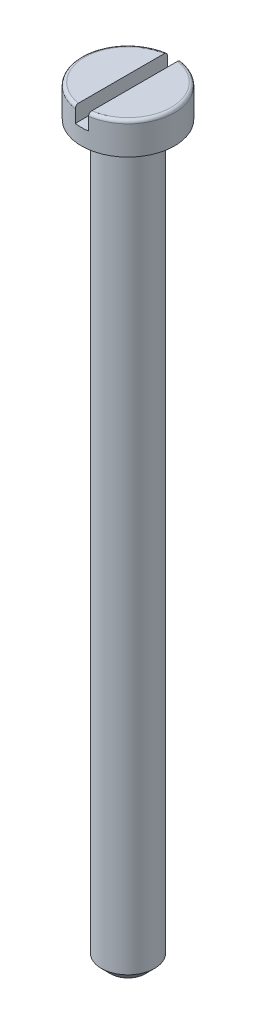
SolidWorks part; units mm, degrees
ref_plane "Face" through (0, 0, 0) normal (0, 0, 1) x (1, 0, 0)
ref_plane "Dessus" through (0, 0, 0) normal (0, 1, 0) x (1, 0, 0)
ref_plane "Droite" through (0, 0, 0) normal (1, 0, 0) x (0, 0, -1)
ref_axis "Axe" through (0, 5.27, 0) along (0, -1, 0)
sketch "Esquisse1" plane through (0, 0, 0) normal (0, 1, 0) x (1, 0, 0)
  circle A0 centre (0, 0) radius 2
  dimension "Diamètre nominal" = 4
extrude "Tige" add sketch "Esquisse1" against normal blind 55
chamfer "Chanfrein d'entrée" distance 0.7 angle 45 1 edges at (0, -55, 2)
sketch "Esquisse2" plane through (0, 0, 0) normal (0, 0, 1) x (1, 0, 0)
  line L0 (-2.75, 0) -> (4.25, 0) construction
  line L2 (0, 0) -> (3.5, 0)
  line L3 (0, 0) -> (0, 2.4)
  line L4 (0, 2.4) -> (3.26, 2.4)
  line L5 (3.5, 0) -> (3.5, 2.16)
  line L7 (0, 2.4) -> (0, -6) construction
  line L10 (1.25, 0) -> (-1.25, 0) construction
  arc A0 (3.5, 2.16) -> (3.26, 2.4) centre (3.26, 2.16) ccw
  dimension "D2" = 0.24
  dimension "Diamètre tête" = 7
  dimension "D1" = 3.5
  dimension "Hauteur tête" = 2.4
revolve "Tête" add sketch "Esquisse2" angle 360 about L7
sketch "Esquisse3" plane through (0, 2.4, -1.8) normal (0, -1, 0) x (1, 0, 0)
  line L0 (0, -1.7) -> (0, 5.3) construction
  line L1 (0.5, -1.7) -> (-0.5, -1.7)
  line L2 (0.5, 5.3) -> (-0.5, 5.3)
  line L3 (0.5, -1.7) -> (0.5, 5.3)
  line L4 (-0.5, -1.7) -> (-0.5, 5.3)
  circle A1 centre (0, 1.8) radius 3.5 construction
  dimension "Largeur fente" = 1
extrude "Fente" cut sketch "Esquisse3" along normal blind 1.2
equation "\"D1@Esquisse2\" = \"Diamètre tête@Esquisse2\"/2"
equation "\"D2@Esquisse2\" = \"Hauteur tête@Esquisse2\"*0.1"
equation "\"D1@Fente\" = \"Hauteur tête@Esquisse2\"/2"
